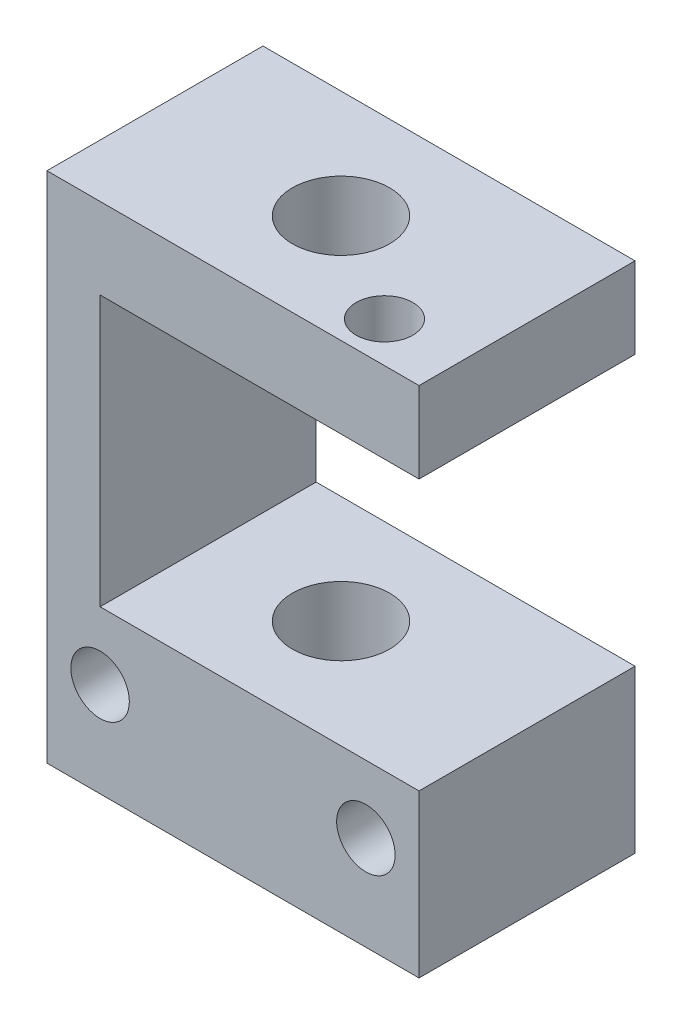
SolidWorks part; units mm, degrees
ref_plane "Front Plane" through (0, 0, 0) normal (0, 0, 1) x (1, 0, 0)
ref_plane "Top Plane" through (0, 0, 0) normal (0, 1, 0) x (1, 0, 0)
ref_plane "Right Plane" through (0, 0, 0) normal (1, 0, 0) x (0, 0, -1)
sketch "Sketch2" plane through (0, 0, 0) normal (0, 1, 0) x (1, 0, 0)
  line L1 (0, 0) -> (35, 0)
  line L2 (0, 0) -> (0, 20.32)
  line L3 (0, 20.32) -> (35, 20.32)
  line L4 (35, 0) -> (35, 20.32)
  circle A0 centre (17.5, 10.16) radius 4.572
  point P8 (17.5, 20.32)
  point P9 (0, 10.16)
  dimension "D3" = 9.144
  dimension "D1" = 35
  dimension "D2" = 20.32
extrude "Boss-Extrude1" add sketch "Sketch2" along normal blind 48.26
hole_wizard "M5 Clearance Hole1" positions "Sketch3" profile "Sketch4" hole size "M5" standard "ANSI Metric" end condition through all
sketch "Sketch3" plane through (0, 0, 0) normal (0, 0, 1) x (1, 0, 0)
  line L0 (5, 8.89) -> (30, 8.89) construction
  line L2 (0, 0) -> (35, 0) construction
  point P0 (5, 8.89)
  point P2 (30, 8.89)
  point P9 (17.5, 0)
  point P10 (17.5, 8.89)
  dimension "D1" = 25
  dimension "D2" = 8.89
sketch "Sketch4" plane through (5, 8.89, 0) normal (1, 0, 0) x (0, -1, 0)
  line L0 (0, 0) -> (0, 20.32)
  line L1 (0, 20.32) -> (2.75, 20.32)
  line L2 (2.75, 20.32) -> (2.75, 0)
  line L5 (2.75, 0) -> (0, 0)
  line L11 (0, -6.35) -> (0, 107.95) construction
  dimension "Thru Hole Dia." = 5.5
  dimension "Thru Hole Depth" = 20.32
sketch "Sketch7" plane through (0, 48.26, 0) normal (0, 1, 0) x (1, 0, 0)
  line L0 (0, 0) -> (35, 0) construction
  circle A0 centre (27.94, 3.81) radius 2.667
  dimension "D3" = 5.334
  dimension "D1" = 27.94
  dimension "D2" = 3.81
extrude "Cut-Extrude1" cut sketch "Sketch7" against normal blind 5
sketch "Sketch8" plane through (0, 0, -20.32) normal (0, 0, -1) x (-1, 0, 0)
  line L0 (-35, 48.26) -> (-35, 0) construction
  line L1 (-35, 40.64) -> (-5, 40.64)
  line L2 (-35, 40.64) -> (-35, 15.24)
  line L3 (-35, 15.24) -> (-5, 15.24)
  line L4 (-5, 40.64) -> (-5, 15.24)
  line L6 (0, 48.26) -> (0, 0) construction
  circle A0 centre (-30, 8.89) radius 2.75 construction
  dimension "D2" = 6.35
  dimension "D1" = 25.4
  dimension "D3" = 5
extrude "Cut-Extrude2" cut sketch "Sketch8" against normal through all
equation "\"press fit\"= 0.3mm"
equation "\"pin diamiter\"= 5mm"
equation "\"D3@Sketch7\"=\"pin diamiter\"+\"press fit\""
equation "\"marker diamiter + a little\"= 0.35in"
equation "\"D3@Sketch2\"=\"marker diamiter + a little\"+\"press fit\""
